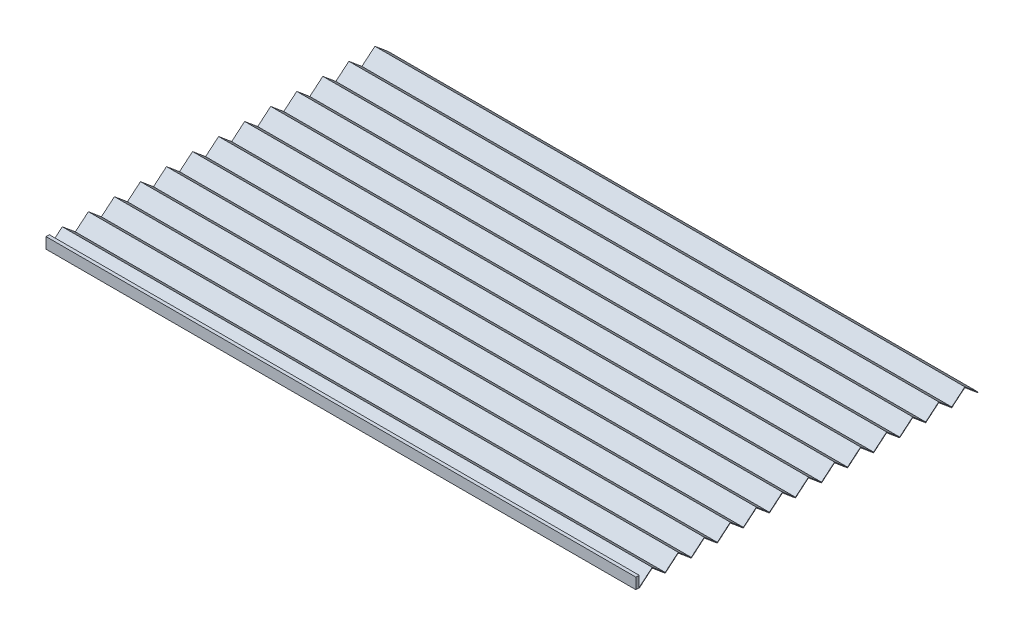
SolidWorks part; units mm, degrees
ref_plane "Front Plane" through (0, 0, 0) normal (0, 0, 1) x (1, 0, 0)
ref_plane "Top Plane" through (0, 0, 0) normal (0, 1, 0) x (1, 0, 0)
ref_plane "Right Plane" through (0, 0, 0) normal (1, 0, 0) x (0, 0, -1)
sketch "Sketch2" plane through (0, 0, 0) normal (0, 0, 1) x (1, 0, 0)
  line L1 (-270, 10) -> (270, 10)
  line L2 (-270, 10) -> (-270, 0)
  line L3 (-270, 0) -> (270, 0)
  line L4 (270, 10) -> (270, 0)
  point P4 (0, 0)
  dimension "D1" = 10
  dimension "D2" = 540
extrude "Boss-Extrude1" add sketch "Sketch2" along normal blind 3
sketch "Sketch3" plane through (270, 0, 0) normal (1, 0, 0) x (0, 0, -1)
  line L0 (0, 10) -> (310.024, 10) construction
  line L1 (0, 0) -> (310.024, 0) construction
  line L2 (310.024, 10) -> (310.024, 0) construction
  line L3 (0, 0) -> (11.924, 10)
  line L4 (11.924, 10) -> (23.848, 0)
  line L5 (23.848, 0) -> (35.772, 10)
  line L6 (35.772, 10) -> (47.696, 0)
  line L7 (47.696, 0) -> (59.62, 10)
  line L8 (59.62, 10) -> (71.544, 0)
  line L9 (71.544, 0) -> (83.468, 10)
  line L10 (83.468, 10) -> (95.392, 0)
  line L11 (95.392, 0) -> (107.316, 10)
  line L12 (107.316, 10) -> (119.24, 0)
  line L13 (119.24, 0) -> (131.164, 10)
  line L14 (131.164, 10) -> (143.088, 0)
  line L15 (143.088, 0) -> (155.012, 10)
  line L16 (155.012, 10) -> (166.936, 0)
  line L17 (166.936, 0) -> (178.86, 10)
  line L18 (178.86, 10) -> (190.784, 0)
  line L20 (190.784, 0) -> (202.708, 10)
  line L21 (202.708, 10) -> (214.632, 0)
  line L22 (214.632, 0) -> (226.556, 10)
  line L23 (226.556, 10) -> (238.48, 0)
  line L24 (238.48, 0) -> (250.404, 10)
  line L25 (250.404, 10) -> (262.328, 0)
  line L26 (262.328, 0) -> (274.252, 10)
  line L27 (274.252, 10) -> (286.176, 0)
  line L28 (286.176, 0) -> (298.1, 10)
  line L29 (298.1, 10) -> (310.024, 0)
  line L30 (310.024, 10) -> (310.024, 0) construction
extrude "Extrude-Thin1" add sketch "Sketch3" against normal through all thin thin type mid plane wall 0.5
